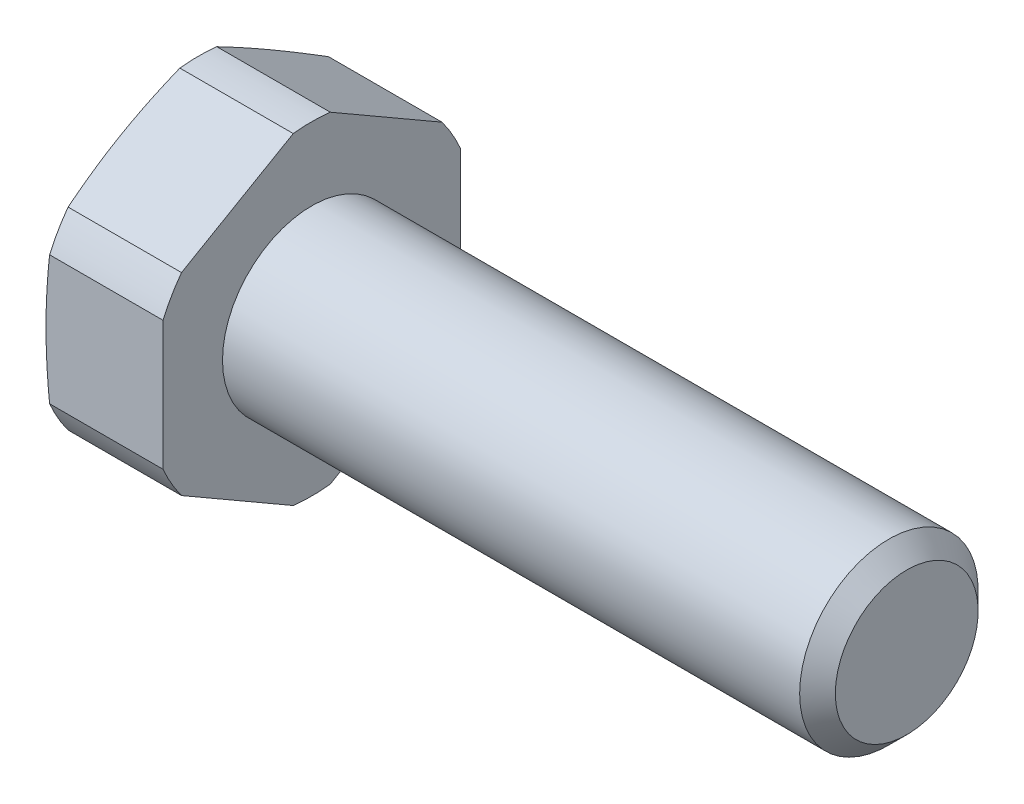
SolidWorks part; units mm, degrees
material "AISI 1020"
ref_plane "Спереди" through (0, 0, 0) normal (0, 0, 1) x (1, 0, 0)
ref_plane "Сверху" through (0, 0, 0) normal (0, 1, 0) x (1, 0, 0)
ref_plane "Справа" through (0, 0, 0) normal (1, 0, 0) x (0, 0, -1)
sketch "Эскиз1" plane through (0, 0, 0) normal (0, 0, 1) x (1, 0, 0)
  line L0 (-1000, 0) -> (49000, 0) construction
  line L1 (-4, 0) -> (-4, 4.75)
  line L2 (-4, 4.75) -> (-3.8124, 5.45)
  line L3 (-3.8124, 5.45) -> (0, 5.45)
  line L4 (0, 5.45) -> (0, 3)
  line L5 (0, 3) -> (19.4, 3)
  line L6 (20, 2.4) -> (20, 0)
  line L7 (20, 3) -> (20.5, 3.866) construction
  line L8 (20.5, 3.866) -> (21, 3) construction
  line L9 (21, 3) -> (20, 3) construction
  line L10 (20.5, 3.866) -> (20.5, 3) construction
  line L11 (20.5, 3.866) -> (2.5, 3.866) construction
  line L12 (19.4, 3) -> (20, 2.4)
  line L13 (20, 3) -> (19.7, 2.7) construction
  line L14 (-4, 4.75) -> (-14, 4.75) construction
  line L15 (-4, 0) -> (20, 0)
  dimension "D1" = 0.6
  dimension "D2" = 15
revolve "Повернуть1" add sketch "Эскиз1" angle 360 about L0
cosmetic thread "Условное изображение резьбы1" parameters "D1"=18, "D2"=4.2679
sketch "Эскиз2" plane through (-4, 0, 0) normal (-1, 0, 0) x (0, 0, 1)
  line L1 (0, 5.7735) -> (-5, 2.8868)
  line L2 (-5, 2.8868) -> (-5, -2.8868)
  line L3 (-5, -2.8868) -> (0, -5.7735)
  line L4 (0, -5.7735) -> (5, -2.8868)
  line L5 (5, -2.8868) -> (5, 2.8868)
  line L6 (5, 2.8868) -> (0, 5.7735)
  circle A0 centre (0, 0) radius 5 construction
  dimension "D1" = 10
extrude "Вырез-Вытянуть1" cut sketch "Эскиз2" against normal up to surface (24 mm away) flip side to cut up to face at (20, 0, 2.4)
equation "\"D1@Эскиз1\"=\"_d_@Эскиз1\"/10"
equation "\"D@Эскиз1\"=\"S_@Эскиз1\"*0.95"
equation "\"D1@Эскиз2\"=\"S_@Эскиз1\""
equation "\"D1@Условное изображение резьбы1\"=\"b_@Эскиз1\""
equation "\"D2@Условное изображение резьбы1\"=\"_d_@Эскиз1\"-\"dr@Эскиз1\"*2"
